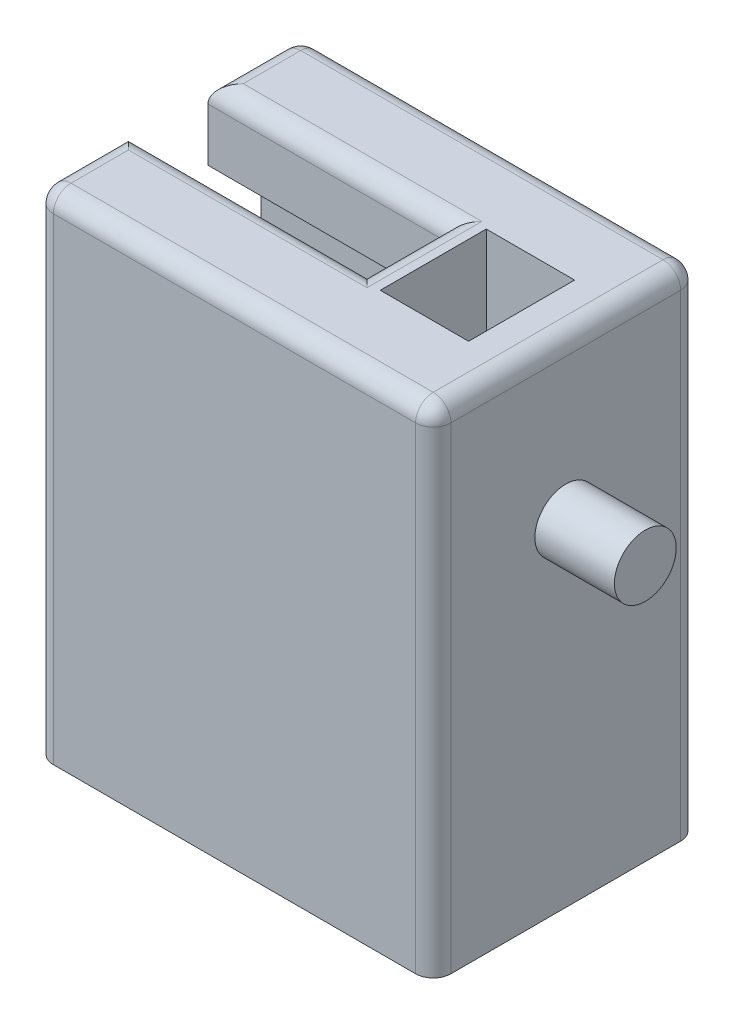
SolidWorks part; units mm, degrees
ref_plane "Plan de face" through (0, 0, 0) normal (0, 0, 1) x (1, 0, 0)
ref_plane "Plan de dessus" through (0, 0, 0) normal (0, 1, 0) x (1, 0, 0)
ref_plane "Plan de droite" through (0, 0, 0) normal (1, 0, 0) x (0, 0, -1)
sketch "Esquisse1" plane through (0, 0, 0) normal (0, 1, 0) x (1, 0, 0)
  line L0 (0, 0) -> (0, 15) construction
  line L1 (0, 0) -> (57, 0) construction
  line L2 (6, 15) -> (6, -15) construction
  line L3 (-16.5, -15) -> (28.5, -15)
  line L4 (-16.5, -15) -> (-16.5, 15)
  line L5 (-16.5, 15) -> (28.5, 15)
  line L6 (28.5, -15) -> (28.5, 15)
  point P8 (28.5, 0)
  dimension "D1" = 30
  dimension "D2" = 45
  dimension "D3" = 6
extrude "Boss.-Extru.1" add sketch "Esquisse1" along normal blind 8
sketch "Esquisse5" plane through (-16.5, 0, 0) normal (-1, 0, 0) x (0, 0, 1)
  line L0 (-15, 8) -> (-15, 56)
  line L1 (-15, 56) -> (15, 56)
  line L2 (15, 56) -> (15, 8)
  line L3 (-15, 8) -> (15, 8)
  dimension "D1" = 48
extrude "Boss.-Extru.3" add sketch "Esquisse5" against normal up to surface (45 mm away) up to face at (28.5, 4, 0)
sketch "Esquisse6" plane through (-16.5, 0, 0) normal (-1, 0, 0) x (0, 0, 1)
  line L2 (10.5, 48) -> (4.5, 48)
  line L3 (-10.5, 48) -> (-10.5, 8)
  line L4 (-10.5, 8) -> (10.5, 8)
  line L5 (10.5, 8) -> (10.5, 48)
  line L6 (0, 0) -> (0, 56) construction
  line L7 (-15, 0) -> (15, 0) construction
  line L8 (15, 56) -> (-15, 56) construction
  line L9 (-15, 28) -> (15, 28) construction
  line L10 (-15, 56) -> (-15, 0) construction
  line L11 (15, 56) -> (15, 0) construction
  line L12 (4.5, 48) -> (4.5, 56)
  line L13 (4.5, 56) -> (-4.5, 56)
  line L14 (-4.5, 56) -> (-4.5, 48)
  line L15 (-4.5, 48) -> (-10.5, 48)
  point P11 (0, 8)
  point P20 (0, 28)
  point P25 (0, 56)
  dimension "D1" = 21
  dimension "D2" = 9
  dimension "D3" = 40
  dimension "D4" = 8
extrude "Enlèv. mat.-Extru.1" cut sketch "Esquisse6" against normal blind 27 contours L2 L12 L13 L14 L15 L3 L4 L5
sketch "Esquisse7" plane through (-16.5, 0, 0) normal (-1, 0, 0) x (0, 0, 1)
  line L0 (0, 0) -> (0, 8) construction
  line L1 (-15, 0) -> (15, 0) construction
  line L2 (-10.5, 8) -> (10.5, 8) construction
  line L3 (-5, 4) -> (5, 4) construction
  circle A0 centre (-5, 4) radius 1.3509
  circle A1 centre (5, 4) radius 1.3509
  dimension "D1" = 10
  dimension "D2" = 4
sketch "Esquisse16" plane through (28.5, 0, 0) normal (1, 0, 0) x (0, 0, -1)
  line L0 (0, 0) -> (0, 56) construction
  line L1 (-15, 0) -> (15, 0) construction
  line L2 (15, 56) -> (-15, 56) construction
  circle A0 centre (0, 38) radius 3.5
  dimension "D1" = 7
  dimension "D2" = 18
fillet "Congé1" radius 2 12 edges at (28.5, 28, 15) (28.5, 28, -15) (-16.5, 28, 15) (-16.5, 28, -15) (-16.5, 56, -9.75) (-16.5, 56, 9.75) (6, 56, -15) (6, 56, 15) (28.5, 56, 0) (-3, 56, 4.5) (10.5, 56, 0) (-3, 56, -4.5)
extrude "Boss.-Extru.5" add sketch "Esquisse16" along normal blind 9
ref_axis "Axe2" through (0, 52.2109, 0) along (0, -1, 0)
sketch "Esquisse21" plane through (0, 8, 0) normal (0, 1, 0) x (1, 0, 0)
  line L0 (0, 0) -> (0, 23.8533) construction
  line L1 (-7.5, 0) -> (7.5, 0) construction
  point P6 (0, 0)
  dimension "D1" = 15
hole_wizard "Dégagement M32" positions "Esquisse22" profile "Esquisse23" hole size "M3" standard "ISO" end condition through all
sketch "Esquisse22" plane through (0, 8, 0) normal (0, 1, 0) x (1, 0, 0)
  point P0 (-7.5, 0)
  point P3 (7.5, 0)
sketch "Esquisse23" plane through (-7.5, 8, 0) normal (1, 0, 0) x (0, 0, 1)
  line L0 (0, 0) -> (0, 8)
  line L1 (0, 8) -> (1.6, 8)
  line L2 (1.6, 8) -> (1.6, 0)
  line L5 (1.6, 0) -> (0, 0)
  line L11 (0, -6.35) -> (0, 107.95) construction
  dimension "Diamètre du perçage jusqu'au prochain" = 3.2
  dimension "Profondeur du perçage jusqu'au prochain" = 8
ref_axis "Axe3" through (51.1437, 38, 0) along (-1, 0, 0)
sketch "Esquisse24" plane through (-16.5, 0, 0) normal (-1, 0, 0) x (0, 0, 1)
  line L0 (0, 0) -> (0, 8) construction
  line L1 (-13, 0) -> (13, 0) construction
  line L2 (-10.5, 8) -> (10.5, 8) construction
  circle A0 centre (-5, 3.5) radius 2.4931
  circle A1 centre (5, 3.5) radius 2.4931
  dimension "D1" = 4.5
  dimension "D2" = 10
hole_wizard "Dégagement M33" positions "Esquisse25" profile "Esquisse27" hole size "M3" standard "ISO"
sketch "Esquisse25" plane through (-16.5, 0, 0) normal (-1, 0, 0) x (0, 0, 1)
  point P0 (-5, 3.5)
  point P3 (5, 3.5)
sketch "Esquisse27" plane through (-16.5, 3.5, -5) normal (0, 1, 0) x (0, 0, 1)
  line L0 (0, 0) -> (0, 8.9614)
  line L1 (0, 8.9614) -> (1.6, 8)
  line L2 (1.6, 8) -> (1.6, 0)
  line L5 (1.6, 0) -> (0, 0)
  line L10 (0, 8.9614) -> (-1.6, 8) construction
  line L11 (0, -6.35) -> (0, 107.95) construction
  dimension "Diamètre du perçage" = 3.2
  dimension "Profondeur du perçage" = 8
  dimension "Angle de pointe" = 118
sketch "Esquisse28" plane through (0, 56, 0) normal (0, 1, 0) x (1, 0, 0)
  line L0 (0, 0) -> (13.5, 0) construction
  line L2 (23.5, 6) -> (13.5, 6)
  line L3 (23.5, 6) -> (23.5, -6)
  line L4 (23.5, -6) -> (13.5, -6)
  line L5 (13.5, 6) -> (13.5, -6)
  line L6 (23.5, 6) -> (13.5, -6) construction
  line L7 (23.5, -6) -> (13.5, 6) construction
  point P3 (18.5, 0)
  dimension "D1" = 13.5
  dimension "D2" = 10
  dimension "D3" = 12
extrude "Enlèv. mat.-Extru.2" cut sketch "Esquisse28" against normal through all
equation "\"!.00mm\"=40"
